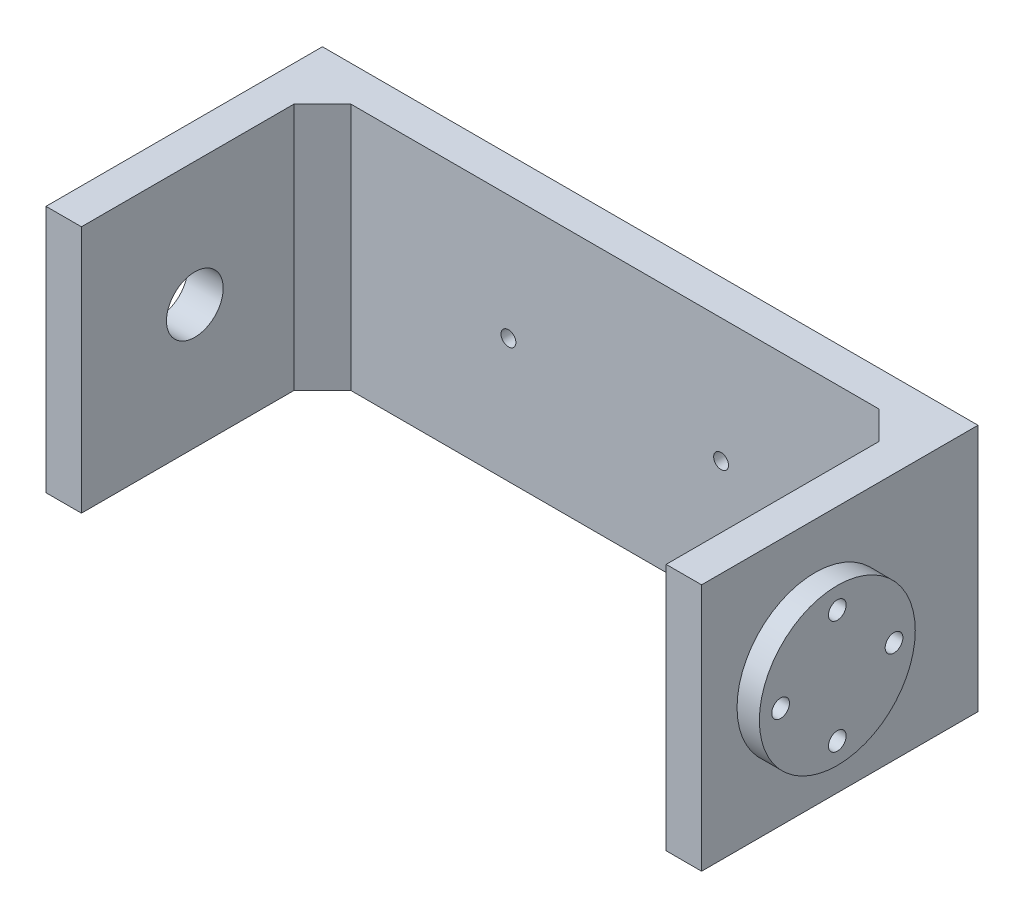
SolidWorks part; units mm, degrees
ref_plane "Front Plane" through (0, 0, 0) normal (0, 0, 1) x (1, 0, 0)
ref_plane "Top Plane" through (0, 0, 0) normal (0, 1, 0) x (1, 0, 0)
ref_plane "Right Plane" through (0, 0, 0) normal (1, 0, 0) x (0, 0, -1)
sketch "Sketch1" plane through (0, 0, 0) normal (0, 1, 0) x (1, 0, 0)
  line L0 (0, 0) -> (0, 39)
  line L1 (0, 39) -> (92.5, 39)
  line L2 (92.5, 39) -> (92.5, 0)
  line L3 (92.5, 0) -> (87.5, 0)
  line L4 (87.5, 0) -> (87.5, 34)
  line L5 (87.5, 34) -> (5, 34)
  line L6 (5, 34) -> (5, 0)
  line L7 (5, 0) -> (0, 0)
  dimension "D1" = 82.5
  dimension "D2" = 5
  dimension "D3" = 5
  dimension "D4" = 39
  dimension "D5" = 34
  dimension "D6" = 39
extrude "Boss-Extrude2" add sketch "Sketch1" along normal blind 35
sketch "Sketch3" plane through (92.5, 0, 0) normal (1, 0, 0) x (0, 0, -1)
  line L2 (16, 6.5) -> (16, 9.5)
  line L6 (0, 0) -> (39, 0)
  line L7 (39, 0) -> (39, 35)
  line L8 (39, 35) -> (0, 35)
  line L9 (0, 35) -> (0, 0)
  line L10 (0, 0) -> (39, 0)
  line L11 (39, 0) -> (39, 35)
  line L12 (39, 35) -> (0, 35)
  line L13 (0, 35) -> (0, 0)
  circle A0 centre (16, 17.5) radius 11
  circle A1 centre (16, 9.5) radius 1.25
  circle A2 centre (8, 17.5) radius 1.25
  circle A3 centre (16, 25.5) radius 1.25
  circle A4 centre (24, 17.5) radius 1.25
  point P17 (16, 17.5)
  dimension "D2" = 22
  dimension "D4" = 2.5
  dimension "D1" = 0
  dimension "D3" = 3
  dimension "D5" = 4
extrude "Boss-Extrude5" add sketch "Sketch3" along normal blind 3.15 contours A1 A0 A4 A3 A2 region at (92.5, 17.5, -16)
sketch "Sketch5" plane through (92.5, 0, 0) normal (1, 0, 0) x (0, 0, -1)
  circle A0 centre (16, 9.5) radius 1.25 construction
  circle A1 centre (24, 17.5) radius 1.25 construction
  circle A2 centre (16, 25.5) radius 1.25 construction
  circle A3 centre (8, 17.5) radius 1.25 construction
  circle A4 centre (16, 9.5) radius 1.25
  circle A5 centre (24, 17.5) radius 1.25
  circle A6 centre (16, 25.5) radius 1.25
  circle A7 centre (8, 17.5) radius 1.25
extrude "Cut-Extrude2" cut sketch "Sketch5" against normal up to next
sketch "Sketch6" plane through (87.5, 0, 0) normal (-1, 0, 0) x (0, 0, 1)
  circle A0 centre (-16, 9.5) radius 2.55
  circle A1 centre (-24, 17.5) radius 2.55
  circle A2 centre (-16, 25.5) radius 2.55
  circle A3 centre (-8, 17.5) radius 2.55
  dimension "D1" = 5.1
  dimension "D2" = 5.1
  dimension "D3" = 5.1
  dimension "D4" = 5.1
extrude "Cut-Extrude3" cut sketch "Sketch6" against normal blind 2.15
sketch "Sketch7" plane through (0, 0, 0) normal (-1, 0, 0) x (0, 0, 1)
  circle A0 centre (-16, 17.5) radius 4
  dimension "D2" = 8
extrude "Cut-Extrude4" cut sketch "Sketch7" against normal up to next
chamfer "Chamfer1" distance 4 angle 45 2 edges at (5, 17.5, -34) (87.5, 17.5, -34)
sketch "Sketch8" plane through (0, 0, -39) normal (0, 0, -1) x (-1, 0, 0)
  line L0 (-46.25, 17.5) -> (-61.25, 17.5)
  line L3 (-46.25, 0) -> (-46.25, 35)
  line L4 (-92.5, 0) -> (0, 0) construction
  line L5 (-92.5, 35) -> (0, 35) construction
  line L6 (-29.25, 16.3453) -> (-31.25, 15.1906)
  line L7 (-61.25, 19.8094) -> (-63.25, 18.6547)
  line L8 (-63.25, 18.6547) -> (-63.25, 16.3453)
  line L9 (-63.25, 16.3453) -> (-61.25, 15.1906)
  line L10 (-61.25, 15.1906) -> (-59.25, 16.3453)
  line L11 (-59.25, 16.3453) -> (-59.25, 18.6547)
  line L12 (-59.25, 18.6547) -> (-61.25, 19.8094)
  line L13 (-29.25, 18.6547) -> (-29.25, 16.3453)
  line L14 (-31.25, 19.8094) -> (-29.25, 18.6547)
  line L15 (-33.25, 18.6547) -> (-31.25, 19.8094)
  line L16 (-33.25, 16.3453) -> (-33.25, 18.6547)
  line L17 (-31.25, 15.1906) -> (-33.25, 16.3453)
  circle A0 centre (-61.25, 17.5) radius 2 construction
  circle A1 centre (-31.25, 17.5) radius 2 construction
  circle A2 centre (-61.25, 17.5) radius 1.05
  circle A3 centre (-31.25, 17.5) radius 1.05
  dimension "D2" = 4
  dimension "D3" = 2.1
  dimension "D4" = 2.1
  dimension "D1" = 15
extrude "Cut-Extrude5" cut sketch "Sketch8" against normal blind 2 contours L11 L12 L7 L8 L9 L10 | L17 L6 L13 L14 L15 L16 region at (59.3111, 16.9226, -39) region at (30.2806, 15.8209, -39)
sketch "Sketch9" plane through (0, 0, -39) normal (0, 0, -1) x (-1, 0, 0)
  circle A0 centre (-61.25, 17.5) radius 1.05 construction
  circle A1 centre (-31.25, 17.5) radius 1.05 construction
  circle A2 centre (-61.25, 17.5) radius 1.05
  circle A3 centre (-31.25, 17.5) radius 1.05
extrude "Cut-Extrude6" cut sketch "Sketch9" against normal up to next
